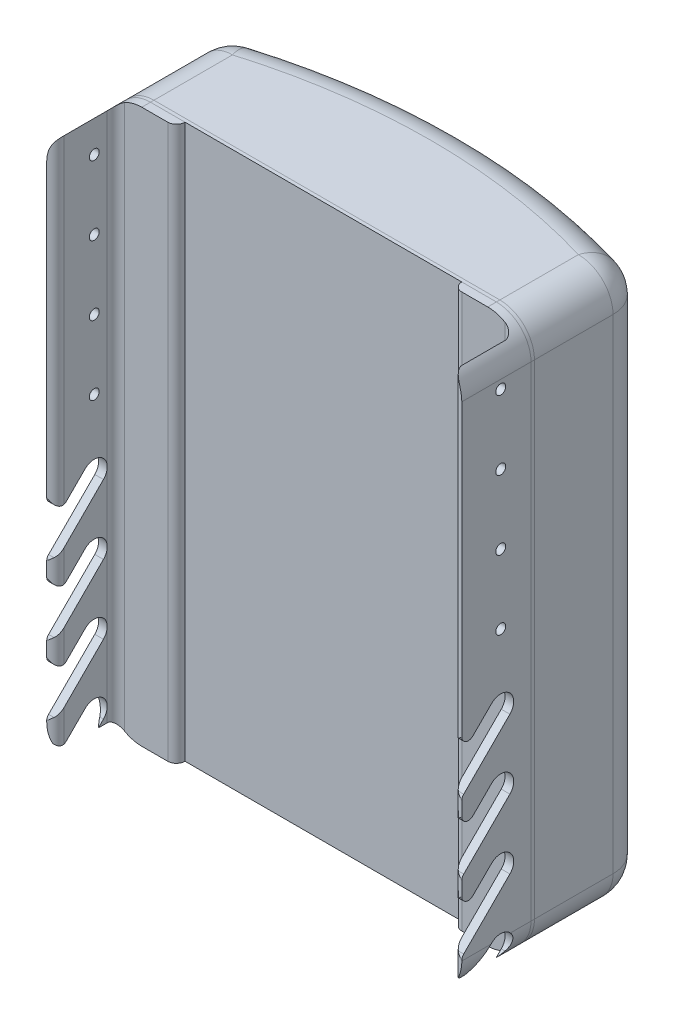
SolidWorks part; units mm, degrees
note: '?' marks a value the reader was unsure of. The reader was unsure of these and kept them because the rebuilt part matched: thickness of "Base-Flange1", "Sheet-Metal21", "Sheet-Metal26".
material "ETHAFOAM"
material "6061-T6 (SS)"
ref_plane "Plane1" through (0, 0, 0) normal (0, 0, 1) x (1, 0, 0)
ref_plane "Plane2" through (0, 0, 0) normal (0, 1, 0) x (1, 0, 0)
ref_plane "Plane3" through (0, 0, 0) normal (1, 0, 0) x (0, 0, -1)
ref_axis "Axis1" through (-83.9706, 0, 0) along (1, 0, 0)?
ref_axis "Axis2" through (0, 0, -6.1057) along (0, 0, 1)?
ref_axis "Axis3" through (0, 111.76, 0) along (0, -1, 0)?
sketch "Sketch14" plane through (0, 0, 0) normal (0, 1, 0) x (1, 0, 0)
  line L10 (76.2, 0) -> (76.2, -22.225)
  line L17 (0, 0) -> (0, -11.191) construction
  line L18 (-76.2, 0) -> (-76.2, -22.225)
  line L19 (76.2, 0) -> (-76.2, 0)
  dimension "D1" = 22.225
  dimension "D2" = 76.2
sketch3d "3DSketch1"
  line L0 (-76.2, 101.6, 0) -> (-76.2, -101.6, 0)
  line L2 (76.2, 101.6, 0) -> (76.2, -101.6, 0)
  dimension "D1" = 203.2
other "Structural Member1" corner treatment miter
ref_plane "Plane4" through (-76.2, 101.6, 0) normal (0, -1, 0) x (1, 0, 0)
sketch "Sketch16" plane through (-73.025, 101.6, 3.175) normal (0, -1, 0) x (1, 0, 0)
  line L0 (0, 3.175) -> (0, 19.05)
  line L2 (-3.175, 22.225) -> (-3.175, -3.175)
  line L3 (-3.175, -3.175) -> (0, 0) construction
  line L4 (22.225, -3.175) -> (-3.175, -3.175)
  line L6 (3.175, 0) -> (19.05, 0)
  arc A0 (0, 19.05) -> (-3.175, 22.225) centre (-3.175, 19.05) ccw
  arc A1 (19.05, 0) -> (22.225, -3.175) centre (19.05, -3.175) cw
  arc A2 (0, 3.175) -> (3.175, 0) centre (3.175, 3.175) ccw
  point P12 (0, 0)
  dimension "D1" = 25.4
  dimension "D2" = 3.175
sketch "Sketch21" plane through (0, 0, 0) normal (1, 0, 0) x (0, 0, -1)
  line L0 (-11.1125, -15.875) -> (-11.1125, -41.275) construction
  line L1 (-11.1125, -41.275) -> (-11.1125, -66.675) construction
  line L2 (-11.1125, -66.675) -> (-11.1125, -92.075) construction
  line L3 (-11.1125, -92.075) -> (-57.027, -92.075) construction
  line L4 (-11.1125, -15.875) -> (-11.1125, 0) construction
  line L5 (-11.1125, 0) -> (0, 0) construction
  line L6 (-57.027, -92.075) -> (-57.027, 9.525) construction
  line L7 (-57.027, 9.525) -> (-11.1125, 9.525) construction
  line L8 (-11.1125, 9.525) -> (-11.1125, 34.925) construction
  line L9 (-11.1125, 34.925) -> (-11.1125, 60.325) construction
  line L10 (-11.1125, 60.325) -> (-11.1125, 85.725) construction
  line L11 (-11.1125, 85.725) -> (-11.1125, 60.325) construction
  line L12 (-11.1125, 0) -> (-11.1125, 9.525) construction
  circle A0 centre (-11.1125, 34.925) radius 1.8288
  circle A1 centre (-11.1125, -92.075) radius 4.7625
  circle A2 centre (-11.1125, -66.675) radius 4.7625
  circle A3 centre (-11.1125, -41.275) radius 4.7625
  circle A4 centre (-11.1125, -15.875) radius 4.7625
  circle A5 centre (-11.1125, 60.325) radius 1.8288
  circle A6 centre (-11.1125, 85.725) radius 1.8288
  circle A7 centre (-11.1125, 9.525) radius 1.8288
  dimension "D1" = 25.4
  dimension "D2" = 9.525
  dimension "D6" = 3.6576
  dimension "D3" = 15.875
  dimension "D4" = 11.1125
  dimension "D5" = 101.6
extrude "Cut-Extrude1" cut sketch "Sketch21" against normal through all both and the other way through all normal cut yes
sketch "Sketch22" plane through (0, 0, 0) normal (1, 0, 0) x (0, 0, -1)
  line L0 (-11.1125, -92.075) -> (-33.5631, -114.5256) construction
  line L1 (-7.7449, -95.4426) -> (-30.1955, -117.8932)
  line L2 (-14.4801, -88.7074) -> (-36.9307, -111.158)
  line L3 (-11.1125, -66.675) -> (-33.5631, -89.1256) construction
  line L4 (-7.7449, -70.0426) -> (-30.1955, -92.4932)
  line L5 (-14.4801, -63.3074) -> (-36.9307, -85.758)
  line L6 (-11.1125, -41.275) -> (-33.5631, -63.7256) construction
  line L7 (-7.7449, -44.6426) -> (-30.1955, -67.0932)
  line L8 (-14.4801, -37.9074) -> (-36.9307, -60.358)
  line L9 (-11.1125, -15.875) -> (-33.5631, -38.3256) construction
  line L10 (-7.7449, -19.2426) -> (-30.1955, -41.6932)
  line L11 (-14.4801, -12.5074) -> (-36.9307, -34.958)
  line L12 (-11.1125, -92.075) -> (-11.1125, -127.9722) construction
  arc A0 (-7.7449, -95.4426) -> (-14.4801, -88.7074) centre (-11.1125, -92.075) ccw
  arc A1 (-36.9307, -111.158) -> (-30.1955, -117.8932) centre (-33.5631, -114.5256) ccw
  arc A2 (-7.7449, -70.0426) -> (-14.4801, -63.3074) centre (-11.1125, -66.675) ccw
  arc A3 (-36.9307, -85.758) -> (-30.1955, -92.4932) centre (-33.5631, -89.1256) ccw
  arc A4 (-7.7449, -44.6426) -> (-14.4801, -37.9074) centre (-11.1125, -41.275) ccw
  arc A5 (-36.9307, -60.358) -> (-30.1955, -67.0932) centre (-33.5631, -63.7256) ccw
  arc A6 (-7.7449, -19.2426) -> (-14.4801, -12.5074) centre (-11.1125, -15.875) ccw
  arc A7 (-36.9307, -34.958) -> (-30.1955, -41.6932) centre (-33.5631, -38.3256) ccw
  circle A8 centre (-11.1125, -66.675) radius 4.7625 construction
  point P3 (-22.3378, -103.3003)
  point P8 (-22.3378, -77.9003)
  point P16 (-22.3378, -52.5003)
  point P24 (-22.3378, -27.1003)
  dimension "D1" = 45
  dimension "D2" = 31.75
extrude "Cut-Extrude2" cut sketch "Sketch22" against normal through all both and the other way through all normal cut yes
sketch "Sketch24" plane through (0, 0, 0) normal (1, 0, 0) x (0, 0, -1)
  line L15 (-7.7449, -95.4426) -> (-13.9023, -101.6)
  line L16 (-13.9023, -101.6) -> (0, -101.6)
  line L17 (0, -101.6) -> (0, 101.6)
  line L18 (0, 101.6) -> (-25.4, 101.6)
  line L19 (-25.4, 101.6) -> (-25.4, -23.4273)
  line L20 (-25.4, -23.4273) -> (-14.4801, -12.5074)
  line L21 (-7.7449, -19.2426) -> (-25.4, -36.8977)
  line L22 (-25.4, -36.8977) -> (-25.4, -48.8273)
  line L23 (-25.4, -48.8273) -> (-14.4801, -37.9074)
  line L24 (-7.7449, -44.6426) -> (-25.4, -62.2977)
  line L25 (-25.4, -62.2977) -> (-25.4, -74.2273)
  line L26 (-25.4, -74.2273) -> (-14.4801, -63.3074)
  line L27 (-7.7449, -70.0426) -> (-25.4, -87.6977)
  line L28 (-25.4, -87.6977) -> (-25.4, -99.6273)
  line L29 (-25.4, -99.6273) -> (-14.4801, -88.7074)
  line L30 (-7.7449, -95.4426) -> (-9.8373, -97.535)
  line L31 (-8.1535, -101.6) -> (0, -101.6)
  line L32 (0, -101.6) -> (0, 101.6)
  line L33 (0, 101.6) -> (-25.4, 101.6)
  line L34 (-25.4, 101.6) -> (-25.4, -17.6785)
  line L35 (-21.335, -19.3623) -> (-14.4801, -12.5074)
  line L36 (-7.7449, -19.2426) -> (-24.7025, -36.2002)
  line L37 (-25.4, -37.884) -> (-25.4, -43.0785)
  line L38 (-21.335, -44.7623) -> (-14.4801, -37.9074)
  line L39 (-7.7449, -44.6426) -> (-24.7025, -61.6002)
  line L40 (-25.4, -63.284) -> (-25.4, -68.4785)
  line L41 (-21.335, -70.1623) -> (-14.4801, -63.3074)
  line L42 (-7.7449, -70.0426) -> (-24.7025, -87.0002)
  line L43 (-25.4, -88.684) -> (-25.4, -93.8785)
  line L44 (-21.335, -95.5623) -> (-14.4801, -88.7074)
  arc A0 (-9.8373, -97.535) -> (-8.1535, -101.6) centre (-8.1535, -99.2188) ccw
  arc A1 (-25.4, -93.8785) -> (-21.335, -95.5623) centre (-23.0188, -93.8785) ccw
  arc A2 (-24.7025, -87.0002) -> (-25.4, -88.684) centre (-23.0188, -88.684) ccw
  arc A3 (-25.4, -68.4785) -> (-21.335, -70.1623) centre (-23.0188, -68.4785) ccw
  arc A4 (-7.7449, -95.4426) -> (-14.4801, -88.7074) centre (-11.1125, -92.075) ccw
  arc A5 (-7.7449, -19.2426) -> (-14.4801, -12.5074) centre (-11.1125, -15.875) ccw
  arc A6 (-7.7449, -44.6426) -> (-14.4801, -37.9074) centre (-11.1125, -41.275) ccw
  arc A7 (-7.7449, -70.0426) -> (-14.4801, -63.3074) centre (-11.1125, -66.675) ccw
  arc A8 (-7.7449, -95.4426) -> (-14.4801, -88.7074) centre (-11.1125, -92.075) ccw
  arc A9 (-7.7449, -19.2426) -> (-14.4801, -12.5074) centre (-11.1125, -15.875) ccw
  arc A10 (-7.7449, -44.6426) -> (-14.4801, -37.9074) centre (-11.1125, -41.275) ccw
  arc A11 (-7.7449, -70.0426) -> (-14.4801, -63.3074) centre (-11.1125, -66.675) ccw
  arc A12 (-24.7025, -61.6002) -> (-25.4, -63.284) centre (-23.0188, -63.284) ccw
  arc A13 (-24.7025, -36.2002) -> (-25.4, -37.884) centre (-23.0188, -37.884) ccw
  arc A14 (-25.4, -43.0785) -> (-21.335, -44.7623) centre (-23.0188, -43.0785) ccw
  arc A15 (-25.4, -17.6785) -> (-21.335, -19.3623) centre (-23.0188, -17.6785) ccw
  dimension "D2" = 2.3813
  dimension "D1" = 0
extrude "Cut-Extrude3" cut sketch "Sketch24" against normal through all both and the other way through all flip side to cut normal cut yes
sketch "Sketch25" plane through (0, 0, 0) normal (0, 0, -1) x (-1, 0, 0)
  line L1 (76.2, -101.6) -> (-76.2, -101.6)
  line L2 (76.2, -101.6) -> (76.2, 101.6)
  line L3 (76.2, 101.6) -> (-76.2, 101.6)
  line L4 (-76.2, -101.6) -> (-76.2, 101.6)
base flange "Base-Flange1" sketch "Sketch25" thickness 1.27 reverse thickness direction yes parameters "D1"=4.7625
sketch "Sketch30" plane through (0, 0, 0) normal (0, 1, 0) x (1, 0, 0)
  line L1 (-76.2, 1.27) -> (76.2, 1.27)
  line L2 (-76.2, 1.27) -> (-76.2, 52.07)
  line L3 (-76.2, 52.07) -> (76.2, 52.07)
  line L4 (76.2, 1.27) -> (76.2, 52.07)
  dimension "D1" = 50.8
extrude "Boss-Extrude1" add sketch "Sketch30" along normal up to vertex (101.6 mm away) and the other way up to vertex (101.6 mm away) separate body up to point (-76.2, 101.6, -1.27) other way up to point (-76.2, -101.6, -1.27)
sketch "Sketch31" plane through (0, 101.6, 0) normal (0, 1, 0) x (1, 0, 0)
  line L0 (-76.2, 52.07) -> (-76.2, 1.27) construction
  line L1 (76.2, 1.27) -> (76.2, 52.07) construction
  line L2 (0, 52.07) -> (0, 1.27) construction
  line L4 (76.2, 52.07) -> (-76.2, 52.07) construction
  line L5 (-76.2, 1.27) -> (76.2, 1.27) construction
  line L6 (-76.2, 39.37) -> (-76.2, 64.77)
  line L7 (-76.2, 64.77) -> (76.2, 64.77)
  line L8 (76.2, 64.77) -> (76.2, 39.37)
  arc A0 (-76.2, 39.37) -> (76.2, 39.37) centre (0, -182.88) cw
  dimension "D1" = 38.1
  dimension "D2" = 25.4
extrude "Cut-Extrude4" cut sketch "Sketch31" against normal through all normal cut yes
fillet "Fillet1" radius 12.7 8 edges at (-76.2, 0, -39.37) (0, -101.6, -52.07) (76.2, 0, -39.37) (0, 101.6, -52.07) (-76.2, -101.6, -20.32) (76.2, -101.6, -20.32) (76.2, 101.6, -20.32) (-76.2, 101.6, -20.32)
sketch "Sketch32" plane through (0, 0, 0) normal (0, 0, 1) x (1, 0, 0)
  line L0 (67.1286, -88.9) -> (76.2, -88.9) construction
  line L4 (-76.2, 101.6) -> (-76.2, -101.6)
  line L5 (76.2, 101.6) -> (-76.2, 101.6)
  line L6 (76.2, -101.6) -> (76.2, 101.6)
  line L7 (-76.2, -101.6) -> (76.2, -101.6)
  line L8 (-76.2, 88.9) -> (-76.2, -88.9)
  line L9 (63.5, 101.6) -> (-63.5, 101.6)
  line L10 (76.2, -88.9) -> (76.2, 88.9)
  line L11 (-63.5, -101.6) -> (63.5, -101.6)
  arc A0 (76.2, -88.9) -> (63.5, -101.6) centre (63.5, -88.9) cw
  arc A1 (-76.2, -88.9) -> (-63.5, -101.6) centre (-63.5, -88.9) ccw
  arc A2 (-76.2, 88.9) -> (-63.5, 101.6) centre (-63.5, 88.9) cw
  arc A3 (63.5, 101.6) -> (76.2, 88.9) centre (63.5, 88.9) cw
  arc A4 (63.5, -101.6) -> (76.2, -88.9) centre (63.5, -88.9) ccw construction
  dimension "D1" = 0
extrude "Cut-Extrude5" cut sketch "Sketch32" along normal through all and the other way through all flip side to cut normal cut yes
sketch "Bend-Lines1" [suppressed] plane through (0, 0, 0) normal (0, 1, 0) x (1, 0, 0)
sketch "Bounding-Box1" [suppressed] plane through (0, 0, 0) normal (0, 1, 0) x (1, 0, 0)
sheet metal parameters "Sheet-Metal21" thickness 1.27 parameters "D1"=4.7625, "D7"=1.5875
flat pattern "Flat-Pattern21" [suppressed]
sketch "Bend-Lines2" plane through (0, 0, 0) normal (0, 1, 0) x (1, 0, 0)
sketch3d "Bounding-Box2" [suppressed]
  line L0 (76.2, 101.6, 0) -> (76.2, -101.6, 0) construction
  line L1 (-76.2, 101.6, 0) -> (-76.2, -101.6, 0) construction
  line L2 (76.2, 101.6, 0) -> (-76.2, 101.6, 0) construction
  line L3 (76.2, -101.6, 0) -> (-76.2, -101.6, 0) construction
sheet metal parameters "Sheet-Metal26" thickness 1.27 parameters "D1"=4.7625, "D7"=1.5875
flat pattern "Flat-Pattern21"
sketch "Bend-Lines2" plane through (0, 0, 0) normal (0, 1, 0) x (1, 0, 0)
sketch3d "Bounding-Box2" [suppressed]
  line L0 (76.2, -101.6, 0) -> (76.2, 101.6, 0) construction
  line L1 (-76.2, -101.6, 0) -> (-76.2, 101.6, 0) construction
  line L2 (76.2, -101.6, 0) -> (-76.2, -101.6, 0) construction
  line L3 (76.2, 101.6, 0) -> (-76.2, 101.6, 0) construction
